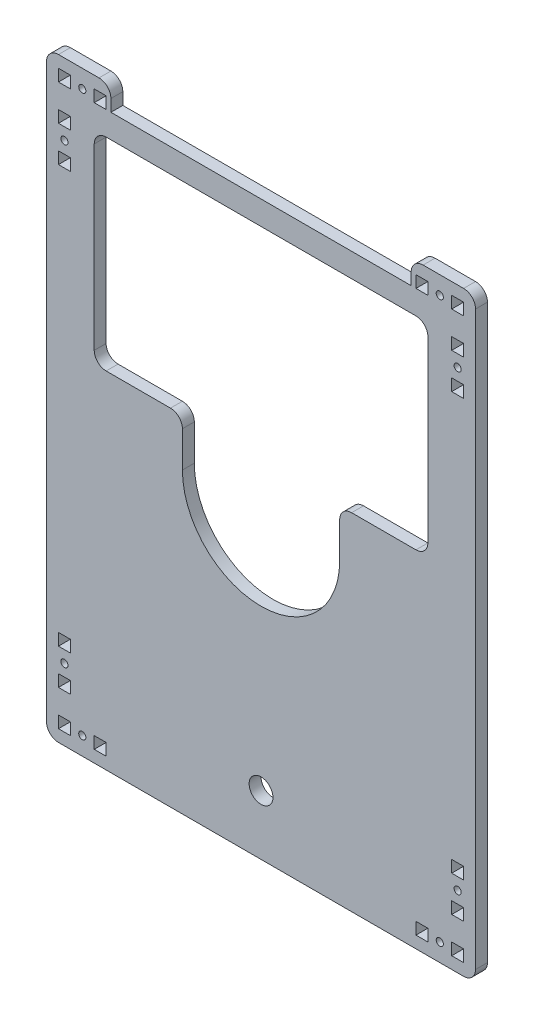
SolidWorks part; units mm, degrees
ref_plane "Front Plane" through (0, 0, 0) normal (0, 0, 1) x (1, 0, 0)
ref_plane "Top Plane" through (0, 0, 0) normal (0, 1, 0) x (1, 0, 0)
ref_plane "Right Plane" through (0, 0, 0) normal (1, 0, 0) x (0, 0, -1)
sketch "Sketch1" plane through (0, 0, 0) normal (0, 0, 1) x (1, 0, 0)
  line L0 (0, 0) -> (187.0096, 0) construction
  line L1 (-90, 125) -> (90, 125) construction
  line L2 (-90, 125) -> (-90, -125)
  line L3 (-90, -125) -> (90, -125)
  line L4 (90, 125) -> (90, -125)
  line L5 (0, 0) -> (0, 134.5508) construction
  line L6 (-90, 117.5) -> (90, 117.5) construction
  line L7 (-70, 105) -> (70, 105)
  line L8 (70, 105) -> (70, 0) construction
  line L9 (70, 0) -> (-70, 0) construction
  line L10 (-70, 0) -> (-70, 105) construction
  line L11 (-70, 0) -> (-33, 0) construction
  line L12 (33, 0) -> (70, 0) construction
  line L13 (82.5, 125) -> (82.5, -125) construction
  line L14 (0, 0) -> (0, -125) construction
  line L15 (-90, 125) -> (-63, 125)
  line L16 (-63, 125) -> (-63, 115)
  line L17 (-63, 115) -> (63, 115)
  line L18 (63, 115) -> (63, 125)
  line L19 (63, 125) -> (90, 125)
  line L20 (-33, 0) -> (-33, 20)
  line L21 (-33, 20) -> (-70, 20)
  line L22 (-70, 20) -> (-70, 105)
  line L23 (33, 0) -> (33, 20)
  line L24 (33, 20) -> (70, 20)
  line L25 (70, 20) -> (70, 105)
  arc A0 (-33, 0) -> (33, 0) centre (0, 0) ccw
  circle A1 centre (0, -100) radius 5
  line B0 (-80, 117.5) -> (-70, 117.5) construction
  line B1 (-80, 120) -> (-85, 120)
  line B2 (-80, 120) -> (-80, 115)
  line B3 (-80, 115) -> (-85, 115)
  line B4 (-85, 120) -> (-85, 115)
  line B5 (-70, 120) -> (-65, 120)
  line B6 (-70, 120) -> (-70, 115)
  line B7 (-70, 115) -> (-65, 115)
  line B8 (-65, 120) -> (-65, 115)
  line B9 (-75, 117.5) -> (-75, 124.4724) construction
  circle B10 centre (-75, 117.5) radius 1.5
  line B11 (-80, -120) -> (-85, -120)
  line B12 (-80, -120) -> (-80, -115)
  line B13 (-80, -115) -> (-85, -115)
  line B14 (-85, -120) -> (-85, -115)
  line B15 (-70, -120) -> (-65, -120)
  line B16 (-70, -120) -> (-70, -115)
  line B17 (-70, -115) -> (-65, -115)
  line B18 (-65, -120) -> (-65, -115)
  circle B19 centre (-75, -117.5) radius 1.5
  line B20 (80, -120) -> (85, -120)
  line B21 (80, -120) -> (80, -115)
  line B22 (80, -115) -> (85, -115)
  line B23 (85, -120) -> (85, -115)
  line B24 (70, -120) -> (65, -120)
  line B25 (70, -120) -> (70, -115)
  line B26 (70, -115) -> (65, -115)
  line B27 (65, -120) -> (65, -115)
  circle B28 centre (75, -117.5) radius 1.5
  line B29 (80, 120) -> (85, 120)
  line B30 (80, 120) -> (80, 115)
  line B31 (80, 115) -> (85, 115)
  line B32 (85, 120) -> (85, 115)
  line B33 (70, 120) -> (65, 120)
  line B34 (70, 120) -> (70, 115)
  line B35 (70, 115) -> (65, 115)
  line B36 (65, 120) -> (65, 115)
  line B37 (75, 117.5) -> (75, 124.4724) construction
  circle B38 centre (75, 117.5) radius 1.5
  line B39 (82.5, 100) -> (82.5, 90) construction
  line B40 (80, 100) -> (80, 105)
  line B41 (80, 100) -> (85, 100)
  line B42 (85, 100) -> (85, 105)
  line B43 (80, 105) -> (85, 105)
  line B44 (80, 90) -> (80, 85)
  line B45 (80, 90) -> (85, 90)
  line B46 (85, 90) -> (85, 85)
  line B47 (80, 85) -> (85, 85)
  line B48 (82.5, 95) -> (75.5276, 95) construction
  circle B49 centre (82.5, 95) radius 1.5
  line B50 (80, -100) -> (80, -105)
  line B51 (80, -100) -> (85, -100)
  line B52 (85, -100) -> (85, -105)
  line B53 (80, -105) -> (85, -105)
  line B54 (80, -90) -> (80, -85)
  line B55 (80, -90) -> (85, -90)
  line B56 (85, -90) -> (85, -85)
  line B57 (80, -85) -> (85, -85)
  circle B58 centre (82.5, -95) radius 1.5
  line B59 (-80, 100) -> (-80, 105)
  line B60 (-80, 100) -> (-85, 100)
  line B61 (-85, 100) -> (-85, 105)
  line B62 (-80, 105) -> (-85, 105)
  line B63 (-80, 90) -> (-80, 85)
  line B64 (-80, 90) -> (-85, 90)
  line B65 (-85, 90) -> (-85, 85)
  line B66 (-80, 85) -> (-85, 85)
  circle B67 centre (-82.5, 95) radius 1.5
  line B68 (-80, -100) -> (-80, -105)
  line B69 (-80, -100) -> (-85, -100)
  line B70 (-85, -100) -> (-85, -105)
  line B71 (-80, -105) -> (-85, -105)
  line B72 (-80, -90) -> (-80, -85)
  line B73 (-80, -90) -> (-85, -90)
  line B74 (-85, -90) -> (-85, -85)
  line B75 (-80, -85) -> (-85, -85)
  circle B76 centre (-82.5, -95) radius 1.5
  dimension "D1" = 150
  dimension "D8" = 33
  dimension "D10" = 10
  dimension "D2" = 7.5
  dimension "D3" = 250
  dimension "D4" = 180
  dimension "D5" = 10
  dimension "D6" = 20
  dimension "D7" = 20
  dimension "D9" = 30
  dimension "D11" = 25
  dimension "D12" = 7.5
  dimension "D13" = 2
sketch_block_instance "Trou M3 plots 5mm-2"
sketch_block "Trou M3 plots 5mm" parameters "D2"=3, "D1"=5, "D3"=5, "D4"=10
sketch_block_instance "Trou M3 plots 5mm-4"
sketch_block_instance "Trou M3 plots 5mm-5"
sketch_block_instance "Trou M3 plots 5mm-6"
sketch_block_instance "Trou M3 plots 5mm-7"
sketch_block_instance "Trou M3 plots 5mm-8"
sketch_block_instance "Trou M3 plots 5mm-9"
sketch_block_instance "Trou M3 plots 5mm-10"
extrude "Boss-Extrude1" add sketch "Sketch1" along normal blind 5
fillet "Fillet1" radius 5 12 edges at (-90, -125, 2.5) (90, -125, 2.5) (90, 125, 2.5) (63, 125, 2.5) (-90, 125, 2.5) (-63, 125, 2.5) (-70, 105, 2.5) (70, 105, 2.5) (70, 20, 2.5) (33, 20, 2.5) (-70, 20, 2.5) (-33, 20, 2.5)
